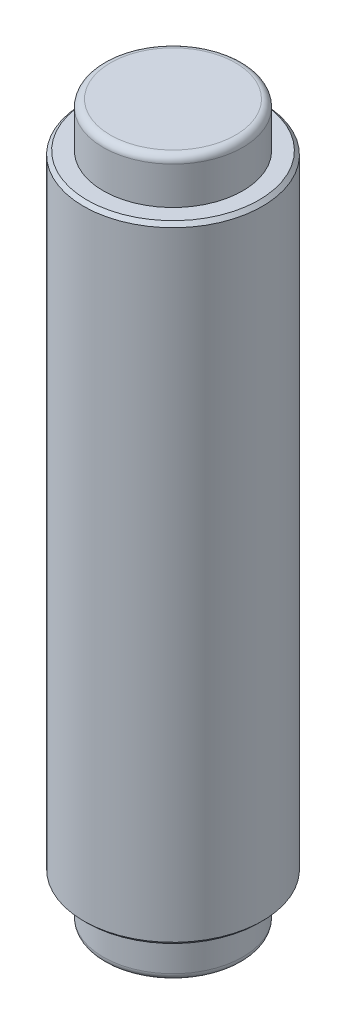
SolidWorks part; units mm, degrees
ref_plane "Front Plane" through (0, 0, 0) normal (0, 0, 1) x (1, 0, 0)
ref_plane "Top Plane" through (0, 0, 0) normal (0, 1, 0) x (1, 0, 0)
ref_plane "Right Plane" through (0, 0, 0) normal (1, 0, 0) x (0, 0, -1)
sketch "Sketch1" plane through (0, 0, 0) normal (0, 1, 0) x (1, 0, 0)
  circle A0 centre (0, 0) radius 3.9
extrude "Boss-Extrude1" add sketch "Sketch1" along normal blind 40
fillet "Fillet5" radius 0.4 2 edges at (0, 0, 3.9) (0, 40, 3.9)
ref_plane "Plane1" through (0, 20, 0) normal (0, 1, 0) x (1, 0, 0)
sketch "Sketch2" plane through (0, 20, 0) normal (0, 1, 0) x (1, 0, 0)
  circle A0 centre (0, 0) radius 5
  dimension "D1" = 10
extrude "Boss-Extrude2" add sketch "Sketch2" along normal mid plane 35
chamfer "Chamfer1" distance 0.2 angle 45 1 edges at (0, 2.5, 5)
chamfer "Chamfer2" distance 0.2 angle 45 1 edges at (0, 37.5, 5)
